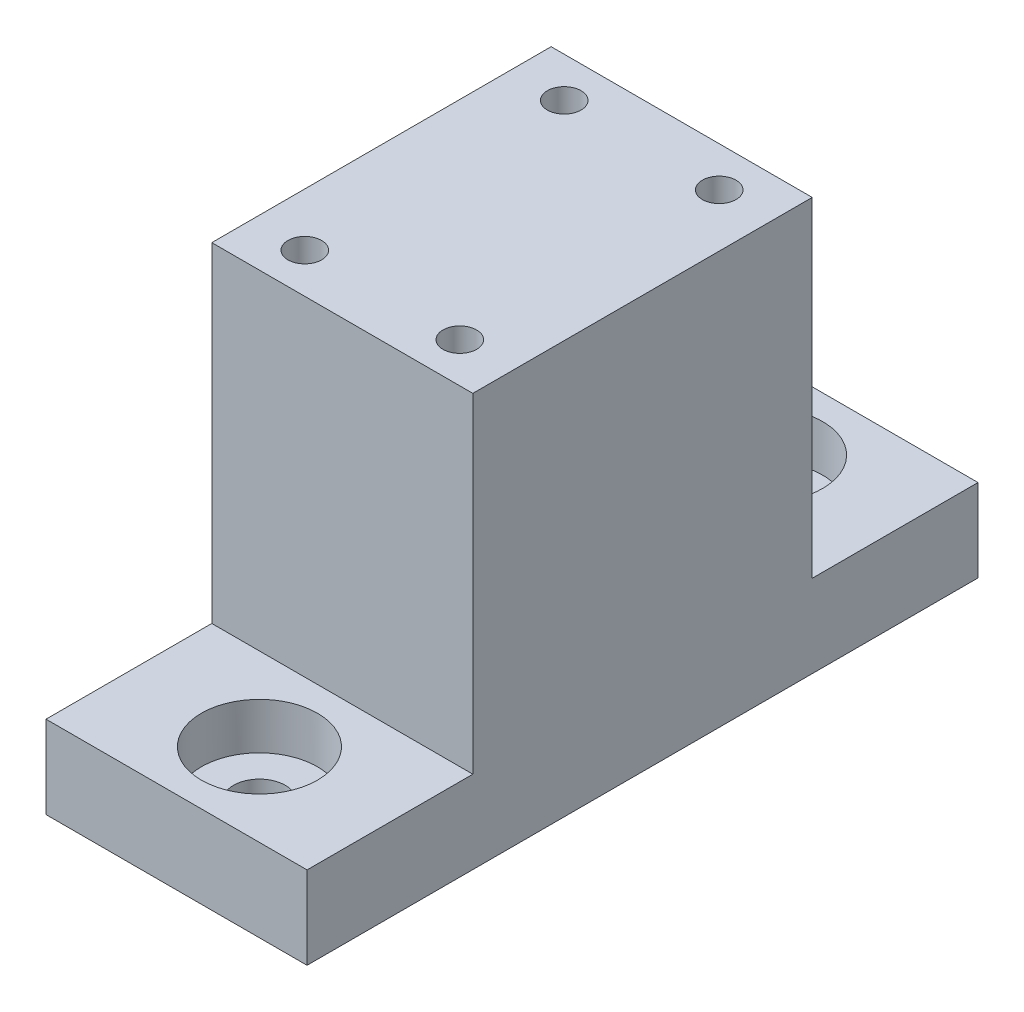
SolidWorks part; units mm, degrees
ref_plane "Front Plane" through (0, 0, 0) normal (0, 0, 1) x (1, 0, 0)
ref_plane "Top Plane" through (0, 0, 0) normal (0, 1, 0) x (1, 0, 0)
ref_plane "Right Plane" through (0, 0, 0) normal (1, 0, 0) x (0, 0, -1)
sketch "Sketch1" plane through (0, 0, 0) normal (1, 0, 0) x (0, 0, -1)
  line L0 (51.4, 0) -> (-51.4, 0)
  line L1 (-51.4, 0) -> (-51.4, 12.6619)
  line L2 (-51.4, 12.6619) -> (-26, 12.6619)
  line L3 (-26, 12.6619) -> (-26, 63.1952)
  line L4 (0, 55) -> (0, -55) construction
  line L5 (26, 12.6619) -> (26, 63.1952)
  line L6 (51.4, 12.6619) -> (26, 12.6619)
  line L7 (51.4, 0) -> (51.4, 12.6619)
  line L8 (26, 63.1952) -> (-26, 63.1952)
  point P12 (0, 0)
  dimension "D1" = 52
  dimension "D2" = 63.1952
  dimension "D3" = 25.4
  dimension "D4" = 12.6619
extrude "Boss-Extrude1" add sketch "Sketch1" along normal blind 39.9999
sketch "Sketch2" plane through (0, 63.1952, 0) normal (0, 1, 0) x (1, 0, 0)
  line L0 (20, 26) -> (20, -26) construction
  line L1 (39.9999, 26) -> (0, 26) construction
  line L2 (39.9999, -26) -> (0, -26) construction
  line L3 (0, 0) -> (39.9999, 0) construction
  line L4 (39.9999, 26) -> (39.9999, -26) construction
  circle A0 centre (8.125, 19.875) radius 2.5797
  circle A1 centre (31.875, 19.875) radius 2.5797
  circle A2 centre (31.875, -19.875) radius 2.5797
  circle A3 centre (8.125, -19.875) radius 2.5797
  circle A4 centre (8.125, 19.875) radius 4.7625
  circle A5 centre (31.875, 19.875) radius 4.7625
  circle A6 centre (8.125, -19.875) radius 4.7625
  circle A7 centre (31.875, -19.875) radius 4.7625
  dimension "D1" = 39.75
  dimension "D3" = 5.1594
  dimension "D4" = 9.525
  dimension "D2" = 23.75
extrude "Cut-Extrude1" cut sketch "Sketch2" against normal through all contours A0 | A1 | A3 | A2 region at (8.125, 63.1952, -19.875) region at (31.875, 63.1952, -19.875) region at (31.875, 63.1952, 19.875) region at (8.125, 63.1952, 19.875)
extrude "Cut-Extrude2" cut sketch "Sketch2<3>" along normal offset from surface (56.8452 mm away) 6.35 from surface up to face at (31.875, 63.1952, 22.4547) starting at face at (31.875, 0, 22.4547)
sketch "Sketch2<3>" plane through (0, 63.1952, 0) normal (0, 1, 0) x (1, 0, 0) same geometry as "Sketch2"
sketch "Sketch3" plane through (0, 12.6619, 0) normal (0, 1, 0) x (1, 0, 0)
  line L0 (39.9999, 51.4) -> (0, 51.4) construction
  line L1 (0, 51.4) -> (0, 26) construction
  line L2 (-22, 0) -> (22, 0) construction
  circle A0 centre (20, 38.7) radius 3.9688
  circle A1 centre (20, 38.7) radius 8.89
  circle A2 centre (20, -38.7) radius 3.9688
  circle A3 centre (20, -38.7) radius 8.89
  point P6 (20, 51.4)
  point P8 (0, 38.7)
  dimension "D1" = 17.78
  dimension "D2" = 7.9375
extrude "Cut-Extrude3" cut sketch "Sketch3" against normal through all contours A0 | A2 region at (20, 12.6619, -38.7)
extrude "Cut-Extrude4" cut sketch "Sketch3<5>" against normal offset from surface (7.1044 mm away) 5.5575 up to face at (31.875, 0, -15.1125)
sketch "Sketch3<5>" plane through (0, 12.6619, 0) normal (0, 1, 0) x (1, 0, 0) same geometry as "Sketch3"
